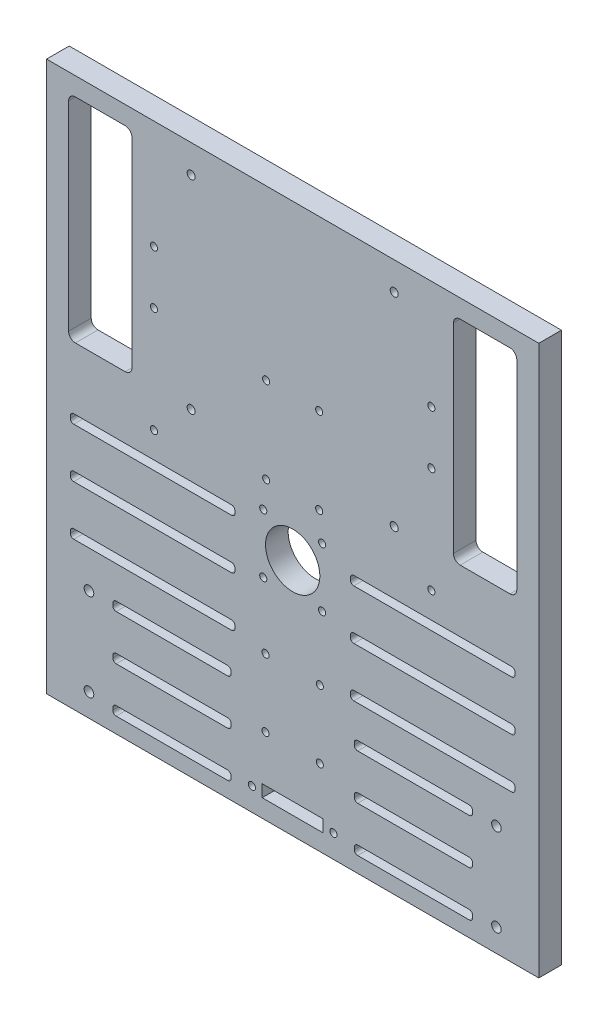
SolidWorks part; units mm, degrees
ref_plane "Front Plane" through (0, 0, 0) normal (0, 0, 1) x (1, 0, 0)
ref_plane "Top Plane" through (0, 0, 0) normal (0, 1, 0) x (1, 0, 0)
ref_plane "Right Plane" through (0, 0, 0) normal (1, 0, 0) x (0, 0, -1)
sketch "Model" plane through (0, 0, 0) normal (0, 0, 1) x (1, 0, 0)
  line L0 (14.2134, -39.9749) -> (14.2134, -38.9749)
  line L1 (-36.5554, -41.4749) -> (12.7134, -41.4749)
  line L2 (-38.0554, -38.9749) -> (-38.0554, -39.9749)
  line L3 (12.7134, -37.4749) -> (-36.5554, -37.4749)
  line L4 (14.2134, -59.9749) -> (14.2134, -58.9749)
  line L5 (-36.5554, -61.4749) -> (12.7134, -61.4749)
  line L6 (-38.0554, -58.9749) -> (-38.0554, -59.9749)
  line L7 (12.7134, -57.4749) -> (-36.5554, -57.4749)
  line L8 (-90.7703, -21.6638) -> (-90.7703, -20.6638)
  line L9 (-161.9933, -23.1638) -> (-92.2703, -23.1638)
  line L10 (-163.4933, -20.6638) -> (-163.4933, -21.6638)
  line L11 (-92.2703, -19.1638) -> (-161.9933, -19.1638)
  line L12 (-90.7703, 22.3362) -> (-90.7703, 23.3362)
  line L13 (-161.9933, 20.8362) -> (-92.2703, 20.8362)
  line L14 (-163.4933, 23.3362) -> (-163.4933, 22.3362)
  line L15 (-92.2703, 24.8362) -> (-161.9933, 24.8362)
  line L16 (-90.7703, 0.3362) -> (-90.7703, 1.3362)
  line L17 (-161.9933, -1.1638) -> (-92.2703, -1.1638)
  line L18 (-163.4933, 1.3362) -> (-163.4933, 0.3362)
  line L19 (-92.2703, 2.8362) -> (-161.9933, 2.8362)
  line L20 (14.2134, -79.9749) -> (14.2134, -78.9749)
  line L21 (-36.5554, -81.4749) -> (12.7134, -81.4749)
  line L22 (-38.0554, -78.9749) -> (-38.0554, -79.9749)
  line L23 (12.7134, -77.4749) -> (-36.5554, -77.4749)
  line L24 (-92.477, -59.9749) -> (-92.477, -58.9749)
  line L25 (-143.2458, -61.4749) -> (-93.977, -61.4749)
  line L26 (-144.7458, -58.9749) -> (-144.7458, -59.9749)
  line L27 (-93.977, -57.4749) -> (-143.2458, -57.4749)
  line L28 (-92.477, -79.9749) -> (-92.477, -78.9749)
  line L29 (-143.2458, -81.4749) -> (-93.977, -81.4749)
  line L30 (-144.7458, -78.9749) -> (-144.7458, -79.9749)
  line L31 (-93.977, -77.4749) -> (-143.2458, -77.4749)
  line L32 (-38.2621, -23.1638) -> (31.4609, -23.1638)
  line L33 (-39.7621, -20.6638) -> (-39.7621, -21.6638)
  line L34 (31.4609, -19.1638) -> (-38.2621, -19.1638)
  line L35 (32.9609, -21.6638) -> (32.9609, -20.6638)
  line L36 (-38.2621, -1.1638) -> (31.4609, -1.1638)
  line L37 (-39.7621, 1.3362) -> (-39.7621, 0.3362)
  line L38 (31.4609, 2.8362) -> (-38.2621, 2.8362)
  line L39 (32.9609, 0.3362) -> (32.9609, 1.3362)
  line L40 (32.9609, 22.3362) -> (32.9609, 23.3362)
  line L41 (-38.2621, 20.8362) -> (31.4609, 20.8362)
  line L42 (-39.7621, 23.3362) -> (-39.7621, 22.3362)
  line L43 (31.4609, 24.8362) -> (-38.2621, 24.8362)
  line L44 (-92.477, -39.9749) -> (-92.477, -38.9749)
  line L45 (-143.2458, -41.4749) -> (-93.977, -41.4749)
  line L46 (-144.7458, -38.9749) -> (-144.7458, -39.9749)
  line L47 (-93.977, -37.4749) -> (-143.2458, -37.4749)
  line L52 (5.7338, 143.3841) -> (5.7338, 55.2603)
  line L53 (30.7338, 146.3841) -> (8.7338, 146.3841)
  line L54 (33.7338, 55.2603) -> (33.7338, 143.3841)
  line L55 (8.7338, 52.2603) -> (30.7338, 52.2603)
  line L56 (-161.2662, 52.2603) -> (-139.2662, 52.2603)
  line L57 (-164.2662, 143.3841) -> (-164.2662, 55.2603)
  line L58 (-139.2662, 146.3841) -> (-161.2662, 146.3841)
  line L59 (-136.2662, 55.2603) -> (-136.2662, 143.3841)
  line L60 (-51.8026, -80.4578) -> (-51.8026, -75.1009)
  line L61 (-51.8026, -80.4578) -> (-78.7298, -80.4578)
  line L62 (-78.7298, -80.4578) -> (-78.7298, -75.1009)
  line L63 (-78.7298, -75.1009) -> (-51.8026, -75.1009)
  line L64 (-173.9912, -88.3391) -> (43.4588, -88.3391)
  line L65 (43.4588, -88.3391) -> (43.4588, 154.5091)
  line L66 (43.4588, 154.5091) -> (-173.9912, 154.5091)
  line L67 (-173.9912, 154.5091) -> (-173.9912, -88.3391)
  arc A0 (14.2134, -38.9749) -> (12.7134, -37.4749) centre (12.7134, -38.9749) ccw
  arc A1 (12.7134, -41.4749) -> (14.2134, -39.9749) centre (12.7134, -39.9749) ccw
  arc A2 (-38.0554, -39.9749) -> (-36.5554, -41.4749) centre (-36.5554, -39.9749) ccw
  arc A3 (-36.5554, -37.4749) -> (-38.0554, -38.9749) centre (-36.5554, -38.9749) ccw
  arc A4 (14.2134, -58.9749) -> (12.7134, -57.4749) centre (12.7134, -58.9749) ccw
  arc A5 (12.7134, -61.4749) -> (14.2134, -59.9749) centre (12.7134, -59.9749) ccw
  arc A6 (-38.0554, -59.9749) -> (-36.5554, -61.4749) centre (-36.5554, -59.9749) ccw
  arc A7 (-36.5554, -57.4749) -> (-38.0554, -58.9749) centre (-36.5554, -58.9749) ccw
  arc A8 (-90.7703, -20.6638) -> (-92.2703, -19.1638) centre (-92.2703, -20.6638) ccw
  arc A9 (-92.2703, -23.1638) -> (-90.7703, -21.6638) centre (-92.2703, -21.6638) ccw
  arc A10 (-163.4933, -21.6638) -> (-161.9933, -23.1638) centre (-161.9933, -21.6638) ccw
  arc A11 (-161.9933, -19.1638) -> (-163.4933, -20.6638) centre (-161.9933, -20.6638) ccw
  arc A12 (-90.7703, 23.3362) -> (-92.2703, 24.8362) centre (-92.2703, 23.3362) ccw
  arc A13 (-92.2703, 20.8362) -> (-90.7703, 22.3362) centre (-92.2703, 22.3362) ccw
  arc A14 (-163.4933, 22.3362) -> (-161.9933, 20.8362) centre (-161.9933, 22.3362) ccw
  arc A15 (-161.9933, 24.8362) -> (-163.4933, 23.3362) centre (-161.9933, 23.3362) ccw
  arc A16 (-90.7703, 1.3362) -> (-92.2703, 2.8362) centre (-92.2703, 1.3362) ccw
  arc A17 (-92.2703, -1.1638) -> (-90.7703, 0.3362) centre (-92.2703, 0.3362) ccw
  arc A18 (-163.4933, 0.3362) -> (-161.9933, -1.1638) centre (-161.9933, 0.3362) ccw
  arc A19 (-161.9933, 2.8362) -> (-163.4933, 1.3362) centre (-161.9933, 1.3362) ccw
  arc A20 (14.2134, -78.9749) -> (12.7134, -77.4749) centre (12.7134, -78.9749) ccw
  arc A21 (12.7134, -81.4749) -> (14.2134, -79.9749) centre (12.7134, -79.9749) ccw
  arc A22 (-38.0554, -79.9749) -> (-36.5554, -81.4749) centre (-36.5554, -79.9749) ccw
  arc A23 (-36.5554, -77.4749) -> (-38.0554, -78.9749) centre (-36.5554, -78.9749) ccw
  arc A24 (-92.477, -58.9749) -> (-93.977, -57.4749) centre (-93.977, -58.9749) ccw
  arc A25 (-93.977, -61.4749) -> (-92.477, -59.9749) centre (-93.977, -59.9749) ccw
  arc A26 (-144.7458, -59.9749) -> (-143.2458, -61.4749) centre (-143.2458, -59.9749) ccw
  arc A27 (-143.2458, -57.4749) -> (-144.7458, -58.9749) centre (-143.2458, -58.9749) ccw
  arc A28 (-92.477, -78.9749) -> (-93.977, -77.4749) centre (-93.977, -78.9749) ccw
  arc A29 (-93.977, -81.4749) -> (-92.477, -79.9749) centre (-93.977, -79.9749) ccw
  arc A30 (-144.7458, -79.9749) -> (-143.2458, -81.4749) centre (-143.2458, -79.9749) ccw
  arc A31 (-143.2458, -77.4749) -> (-144.7458, -78.9749) centre (-143.2458, -78.9749) ccw
  arc A32 (31.4609, -23.1638) -> (32.9609, -21.6638) centre (31.4609, -21.6638) ccw
  arc A33 (-39.7621, -21.6638) -> (-38.2621, -23.1638) centre (-38.2621, -21.6638) ccw
  arc A34 (-38.2621, -19.1638) -> (-39.7621, -20.6638) centre (-38.2621, -20.6638) ccw
  arc A35 (32.9609, -20.6638) -> (31.4609, -19.1638) centre (31.4609, -20.6638) ccw
  arc A36 (31.4609, -1.1638) -> (32.9609, 0.3362) centre (31.4609, 0.3362) ccw
  arc A37 (-39.7621, 0.3362) -> (-38.2621, -1.1638) centre (-38.2621, 0.3362) ccw
  arc A38 (-38.2621, 2.8362) -> (-39.7621, 1.3362) centre (-38.2621, 1.3362) ccw
  arc A39 (32.9609, 1.3362) -> (31.4609, 2.8362) centre (31.4609, 1.3362) ccw
  arc A40 (32.9609, 23.3362) -> (31.4609, 24.8362) centre (31.4609, 23.3362) ccw
  arc A41 (31.4609, 20.8362) -> (32.9609, 22.3362) centre (31.4609, 22.3362) ccw
  arc A42 (-39.7621, 22.3362) -> (-38.2621, 20.8362) centre (-38.2621, 22.3362) ccw
  arc A43 (-38.2621, 24.8362) -> (-39.7621, 23.3362) centre (-38.2621, 23.3362) ccw
  arc A44 (-92.477, -38.9749) -> (-93.977, -37.4749) centre (-93.977, -38.9749) ccw
  arc A45 (-93.977, -41.4749) -> (-92.477, -39.9749) centre (-93.977, -39.9749) ccw
  arc A46 (-144.7458, -39.9749) -> (-143.2458, -41.4749) centre (-143.2458, -39.9749) ccw
  arc A47 (-143.2458, -37.4749) -> (-144.7458, -38.9749) centre (-143.2458, -38.9749) ccw
  arc A76 (8.7338, 146.3841) -> (5.7338, 143.3841) centre (8.7338, 143.3841) ccw
  arc A77 (33.7338, 143.3841) -> (30.7338, 146.3841) centre (30.7338, 143.3841) ccw
  arc A78 (30.7338, 52.2603) -> (33.7338, 55.2603) centre (30.7338, 55.2603) ccw
  arc A79 (5.7338, 55.2603) -> (8.7338, 52.2603) centre (8.7338, 55.2603) ccw
  arc A80 (-164.2662, 55.2603) -> (-161.2662, 52.2603) centre (-161.2662, 55.2603) ccw
  arc A81 (-161.2662, 146.3841) -> (-164.2662, 143.3841) centre (-161.2662, 143.3841) ccw
  arc A82 (-136.2662, 143.3841) -> (-139.2662, 146.3841) centre (-139.2662, 143.3841) ccw
  arc A83 (-139.2662, 52.2603) -> (-136.2662, 55.2603) centre (-139.2662, 55.2603) ccw
  circle A84 centre (-65.2662, 17.0799) radius 12
  circle A85 centre (-47.2662, -78.2141) radius 1.575
  circle A86 centre (-83.2662, -78.2141) radius 1.575
  circle A87 centre (-155.2662, -78.2141) radius 2.125
  circle A88 centre (-155.2662, -39.5701) radius 2.125
  circle A89 centre (-53.2662, -24.6349) radius 1.575
  circle A90 centre (-53.2662, -54.6349) radius 1.575
  circle A91 centre (-77.2662, -24.6349) radius 1.575
  circle A92 centre (-77.2662, -54.6349) radius 1.575
  circle A93 centre (24.7338, -39.5701) radius 2.125
  circle A94 centre (24.7338, -78.2141) radius 2.125
  circle A95 centre (-52.2662, 4.0799) radius 1.575
  circle A96 centre (-52.2662, 30.0799) radius 1.575
  circle A97 centre (-78.2662, 4.0799) radius 1.575
  circle A98 centre (-78.2662, 30.0799) radius 1.575
  circle A99 centre (-3.9918, 82.9719) radius 1.575
  circle A100 centre (-3.9918, 106.4792) radius 1.575
  circle A101 centre (-3.9918, 36.2597) radius 1.575
  circle A102 centre (-20.4162, 142.1299) radius 1.775
  circle A103 centre (-53.5589, 42.2194) radius 1.575
  circle A104 centre (-53.5589, 80.1262) radius 1.575
  circle A105 centre (-20.4162, 52.4299) radius 1.775
  circle A106 centre (-110.1162, 52.4299) radius 1.775
  circle A107 centre (-126.5406, 82.9719) radius 1.575
  circle A108 centre (-126.5406, 106.4792) radius 1.575
  circle A109 centre (-126.5406, 36.2597) radius 1.575
  circle A110 centre (-110.1162, 142.1299) radius 1.775
  circle A111 centre (-76.9734, 42.2194) radius 1.575
  circle A112 centre (-76.9734, 80.1262) radius 1.575
extrude "Boss-Extrude1" add sketch "Model" along normal blind 10
